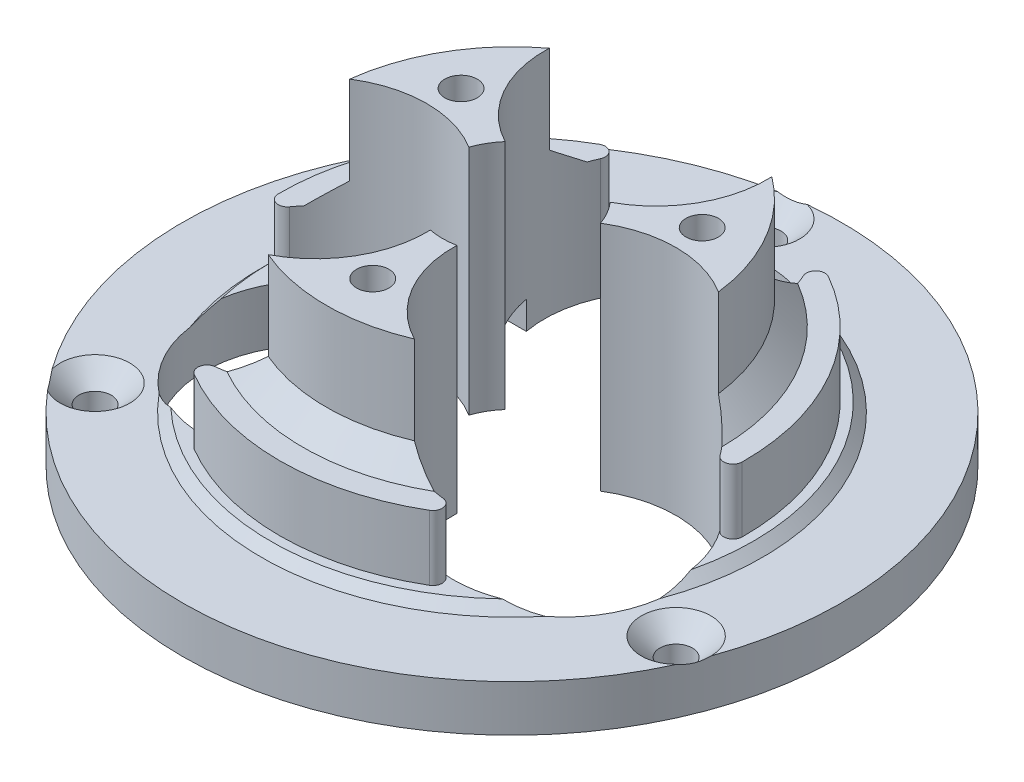
SolidWorks part; units mm, degrees
ref_plane "Front Plane" through (0, 0, 0) normal (0, 0, 1) x (1, 0, 0)
ref_plane "Top Plane" through (0, 0, 0) normal (0, 1, 0) x (1, 0, 0)
ref_plane "Right Plane" through (0, 0, 0) normal (1, 0, 0) x (0, 0, -1)
sketch "Sketch1" plane through (0, 0, 0) normal (0, 1, 0) x (1, 0, 0)
  circle A0 centre (0, 0) radius 35.5
  dimension "D1" = 71
extrude "Boss-Extrude1" add sketch "Sketch1" along normal mid plane 5
sketch "Sketch2" plane through (0, 2.5, 0) normal (0, 1, 0) x (1, 0, 0)
  circle A0 centre (0, 0) radius 26
  dimension "D1" = 52
extrude "Boss-Extrude2" add sketch "Sketch2" along normal blind 1
sketch "Sketch3" plane through (0, 3.5, 0) normal (0, 1, 0) x (1, 0, 0)
  circle A0 centre (0, 0) radius 25
  dimension "D1" = 50
extrude "Boss-Extrude3" add sketch "Sketch3" along normal blind 19
chamfer "Chamfer1" distance 1 angle 45 1 edges at (0, 2.5, 26)
sketch "Sketch4" plane through (0, 22.5, 0) normal (0, 1, 0) x (1, 0, 0)
  line L0 (0, 15.5) -> (0, 0) construction
  line L1 (0, 0) -> (-13.4234, -7.75) construction
  circle A0 centre (0, 15.5) radius 12
  circle A1 centre (13.4234, -7.75) radius 12
  circle A2 centre (-13.4234, -7.75) radius 12
  dimension "D1" = 24
  dimension "D2" = 15.5
  dimension "D3" = 3
extrude "Cut-Extrude1" cut sketch "Sketch4" against normal through all
sketch "Sketch5" plane through (0, 22.5, 0) normal (0, 1, 0) x (1, 0, 0)
  circle A0 centre (0, 0) radius 7.5
  dimension "D1" = 15
extrude "Cut-Extrude2" cut sketch "Sketch5" against normal through all
fillet "Fillet1" radius 1 6 edges at (24.7231, 13, 3.7106) (9.1481, 13, -23.2661) (-9.1481, 13, -23.2661) (-24.7231, 13, 3.7106) (-15.575, 13, 19.5555) (15.575, 13, 19.5555)
sketch "Sketch6" plane through (0, 22.5, 0) normal (0, 1, 0) x (1, 0, 0)
  circle A0 centre (0, 0) radius 30.0189
  circle A1 centre (0, 0) radius 20
  dimension "D1" = 40
extrude "Cut-Extrude3" cut sketch "Sketch6" against normal blind 12
chamfer "Chamfer2" distance 2.5 angle 45 3 edges at (17.3205, 10.5, -10) (-17.3205, 10.5, -10) (0, 10.5, 20)
sketch "Sketch7" plane through (0, 22.5, 0) normal (0, 1, 0) x (1, 0, 0)
  circle A0 centre (0, -15) radius 1.75
  circle A1 centre (-12.9904, 7.5) radius 1.75
  circle A2 centre (12.9904, 7.5) radius 1.75
  dimension "D1" = 15
  dimension "D2" = 3.5
  dimension "D3" = 3
extrude "Cut-Extrude4" cut sketch "Sketch7" against normal through all
sketch "Sketch8" plane through (0, -2.5, 0) normal (0, -1, 0) x (1, 0, 0)
  line L0 (18.8794, -9) -> (17.2339, -6.15)
  line L1 (-1.6454, 17.85) -> (-3.2909, 15)
  line L2 (-3.2909, 15) -> (-1.6454, 12.15)
  line L3 (-1.6454, 12.15) -> (1.6454, 12.15)
  line L4 (1.6454, 12.15) -> (3.2909, 15)
  line L5 (3.2909, 15) -> (1.6454, 17.85)
  line L6 (1.6454, 17.85) -> (-1.6454, 17.85)
  line L7 (17.2339, -6.15) -> (13.943, -6.15)
  line L8 (13.943, -6.15) -> (12.2976, -9)
  line L9 (12.2976, -9) -> (13.943, -11.85)
  line L10 (13.943, -11.85) -> (17.2339, -11.85)
  line L11 (17.2339, -11.85) -> (18.8794, -9)
  line L12 (-14.6358, -13.35) -> (-11.3449, -13.35)
  line L13 (-11.3449, -13.35) -> (-9.6995, -10.5)
  line L14 (-9.6995, -10.5) -> (-11.3449, -7.65)
  line L15 (-11.3449, -7.65) -> (-14.6358, -7.65)
  line L16 (-14.6358, -7.65) -> (-16.2813, -10.5)
  line L17 (-16.2813, -10.5) -> (-14.6358, -13.35)
  circle A0 centre (0, 15) radius 2.85 construction
  circle A1 centre (15.5885, -9) radius 2.85 construction
  circle A2 centre (-12.9904, -10.5) radius 2.85 construction
  dimension "D1" = 5.7
  dimension "D2" = 3
extrude "Cut-Extrude5" cut sketch "Sketch8" against normal blind 3
sketch "Sketch9" plane through (0, 2.5, 0) normal (0, 1, 0) x (1, 0, 0)
  line L0 (0, 0) -> (0, 38.0829) construction
  line L1 (0, 0) -> (-5.8896, 41.9066) construction
  circle A0 centre (-4.4535, 31.6886) radius 1.75
  circle A1 centre (29.6699, -11.9874) radius 1.75
  circle A2 centre (-25.2163, -19.7012) radius 1.75
  dimension "D2" = 3.5
  dimension "D3" = 32
  dimension "D1" = 8
  dimension "D4" = 3
extrude "Cut-Extrude6" cut sketch "Sketch9" against normal through all
chamfer "Chamfer3" distance 2 angle 45 3 edges at (29.6699, 2.5, 13.7374) (-4.4535, 2.5, -29.9386) (-25.2163, 2.5, 21.4512)
